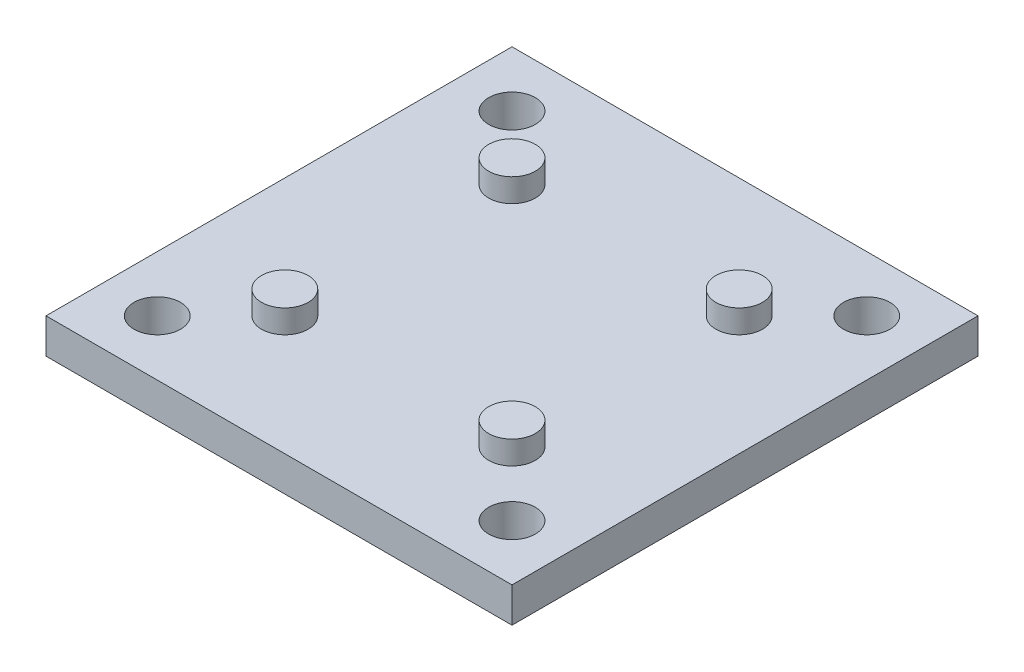
SolidWorks part; units mm, degrees
ref_plane "前视基准面" through (0, 0, 0) normal (0, 0, 1) x (1, 0, 0)
ref_plane "上视基准面" through (0, 0, 0) normal (0, 1, 0) x (1, 0, 0)
ref_plane "右视基准面" through (0, 0, 0) normal (1, 0, 0) x (0, 0, -1)
sketch "草图2" plane through (0, 0, 0) normal (0, 1, 0) x (1, 0, 0)
  line L0 (0, 0) -> (31.047, 0) construction
  line L1 (-9.75, -9.75) -> (9.75, -9.75)
  line L2 (-9.75, -9.75) -> (-9.75, 9.75)
  line L3 (-9.75, 9.75) -> (9.75, 9.75)
  line L4 (9.75, -9.75) -> (9.75, 9.75)
  line L5 (-9.75, -9.75) -> (9.75, 9.75) construction
  line L6 (-9.75, 9.75) -> (9.75, -9.75) construction
  line L7 (-20, -20) -> (20, -20)
  line L8 (-20, -20) -> (-20, 20)
  line L9 (-20, 20) -> (20, 20)
  line L10 (20, -20) -> (20, 20)
  line L11 (-20, -20) -> (20, 20) construction
  line L12 (-20, 20) -> (20, -20) construction
  line L13 (0, 0) -> (0, 17.7315) construction
  circle A0 centre (15.2248, 15.2248) radius 2
  circle A1 centre (-15.2248, -15.2248) radius 2
  circle A2 centre (15.2248, -15.2248) radius 2
  circle A3 centre (-15.2248, 15.2248) radius 2
  circle A4 centre (9.75, 9.75) radius 2
  circle A5 centre (-9.75, 9.75) radius 2
  circle A6 centre (9.75, -9.75) radius 2
  circle A7 centre (-9.75, -9.75) radius 2
  point P0 (0, 0)
  point P6 (0, 0)
  dimension "D5" = 4
  dimension "D7" = 4
  dimension "D8" = 4
  dimension "D9" = 4
  dimension "D10" = 4
  dimension "D1" = 19.5
  dimension "D2" = 19.5
  dimension "D3" = 40
  dimension "D4" = 40
  dimension "D6" = 21.5311
extrude "凸台-拉伸2" add sketch "草图2" along normal blind 3 contours L8 L9 L10 L7
sketch "草图3" plane through (0, 0, 0) normal (0, 1, 0) x (1, 0, 0)
  circle A0 centre (-15.2248, -15.2248) radius 2 construction
  circle A1 centre (15.2248, -15.2248) radius 2 construction
  circle A2 centre (15.2248, 15.2248) radius 2 construction
  circle A3 centre (-15.2248, 15.2248) radius 2 construction
  circle A4 centre (-15.2248, -15.2248) radius 2
  circle A5 centre (15.2248, -15.2248) radius 2
  circle A6 centre (15.2248, 15.2248) radius 2
  circle A7 centre (-15.2248, 15.2248) radius 2
extrude "切除-拉伸1" cut sketch "草图3" along normal blind 3
extrude "凸台-拉伸3" add sketch "草图2<6>" along normal blind 5 contours A5 | A4 | A7 | A6
sketch "草图2<6>" plane through (0, 0, 0) normal (0, 1, 0) x (1, 0, 0) same geometry as "草图2"
